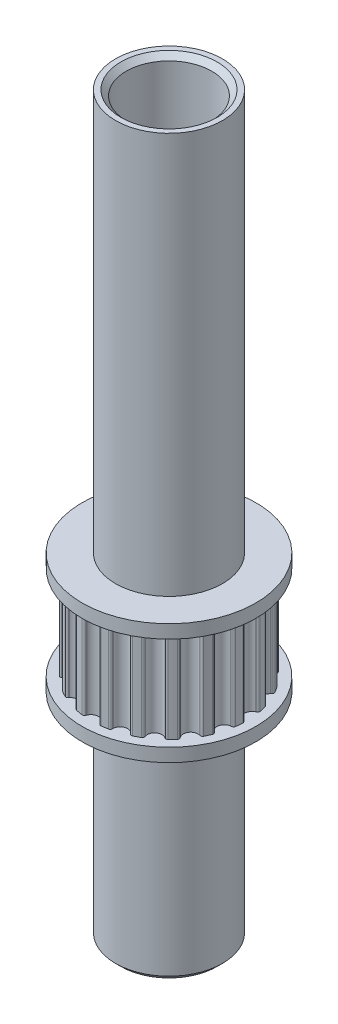
SolidWorks part; units mm, degrees
ref_plane "Front Plane" through (0, 0, 0) normal (0, 0, 1) x (1, 0, 0)
ref_plane "Top Plane" through (0, 0, 0) normal (0, 1, 0) x (1, 0, 0)
ref_plane "Right Plane" through (0, 0, 0) normal (1, 0, 0) x (0, 0, -1)
sketch "Sketch1" plane through (0, 0, 0) normal (0, 1, 0) x (1, 0, 0)
  circle A0 centre (0, 0) radius 4
  circle A1 centre (0, 0) radius 3.2
  dimension "D1" = 8
  dimension "D2" = 0.8
extrude "Boss-Extrude1" add sketch "Sketch1" along normal blind 55
ref_plane "Plane1" through (0, 17, 0) normal (0, 1, 0) x (1, 0, 0)
sketch "Sketch2" plane through (0, 17, 0) normal (0, 1, 0) x (1, 0, 0)
  circle A0 centre (0, 0) radius 6
  circle A1 centre (0, 0) radius 4
  dimension "D1" = 12
extrude "Boss-Extrude2" add sketch "Sketch2" along normal blind 7
sketch "Sketch3" plane through (0, 17, 0) normal (0, -1, 0) x (1, 0, 0)
  circle A0 centre (0, 0) radius 4
  circle A1 centre (0, 0) radius 6.5
  circle A2 centre (0, 0) radius 4 construction
  dimension "D1" = 13
extrude "Boss-Extrude3" add sketch "Sketch3" along normal blind 1 separate body
sketch "Sketch6" plane through (0, 17, 0) normal (0, 1, 0) x (1, 0, 0)
  line L0 (0, 0) -> (0, 8.1681) construction
  line L1 (-0.0071, -0.0407) -> (0.9465, 5.4303) construction
  line L2 (-0.0099, -0.04) -> (1.3906, 5.6439) construction
  line L3 (0, 5.795) -> (0, 6.6155)
  line L4 (1.9605, 5.4533) -> (2.2381, 6.2254)
  arc A1 (0.2982, 5.7873) -> (0, 5.795) centre (0, 0) ccw
  arc A2 (0.2982, 5.7873) -> (0.439, 5.6587) centre (0.2905, 5.6375) cw
  arc A3 (0.439, 5.6587) -> (0.4521, 5.586) centre (1.429, 5.7996) ccw
  arc A4 (0.4521, 5.586) -> (1.4644, 5.4096) centre (0.9943, 5.7045) ccw
  circle A5 centre (0, 0) radius 5.2355 construction
  circle A6 centre (0, 0) radius 5.795 construction
  arc A7 (-1.5827, -6.4234) -> (-1.1359, -6.5173) centre (0, 0) ccw
  arc A8 (1.5013, 5.4735) -> (1.4644, 5.4096) centre (0.6173, 5.941) cw
  arc A9 (1.6773, 5.5469) -> (1.5013, 5.4735) centre (1.6339, 5.4034) ccw
  arc A10 (1.6773, 5.5469) -> (1.9605, 5.4533) centre (0, 0) cw
  arc A11 (2.2381, 6.2254) -> (0, 6.6155) centre (0, 0) ccw
  circle A12 centre (0, 0) radius 6.6155 construction
  point P15 (1.3864, 5.6267)
  point P16 (0.995, 5.7089)
  point P18 (6.3265, 1.9342)
  dimension "D1" = 1.38
  dimension "D2" = 0.15
  dimension "D3" = 1
  dimension "D4" = 0.555
  dimension "D7" = 11.59
  dimension "D6" = 0.4
  dimension "D5" = 1.38
  dimension "D8" = 1
extrude "Cut-Extrude1" cut sketch "Sketch6" along normal blind 7 contours L4 A11 L3 A1 A2 A3 A4 A8 A9 A10 region at (1.0383, 17, -5.9574)
ref_axis "Axis1" through (0, 55, 0) along (0, -1, 0)
pattern_circular "CirPattern1" count 19 over 360 about axis through (0, 55, 0) along (0, -1, 0) of "Cut-Extrude1"
sketch "Sketch4" plane through (0, 24, 0) normal (0, 1, 0) x (1, 0, 0)
  circle A0 centre (0, 0) radius 6.5
  circle A1 centre (0, 0) radius 4
  dimension "D1" = 13
extrude "Boss-Extrude4" add sketch "Sketch4" along normal blind 1
chamfer "Chamfer1" distance 0.4 angle 45 1 edges at (0, 0, 4)
chamfer "Chamfer2" distance 0.4 angle 45 1 edges at (0, 55, 3.2)
